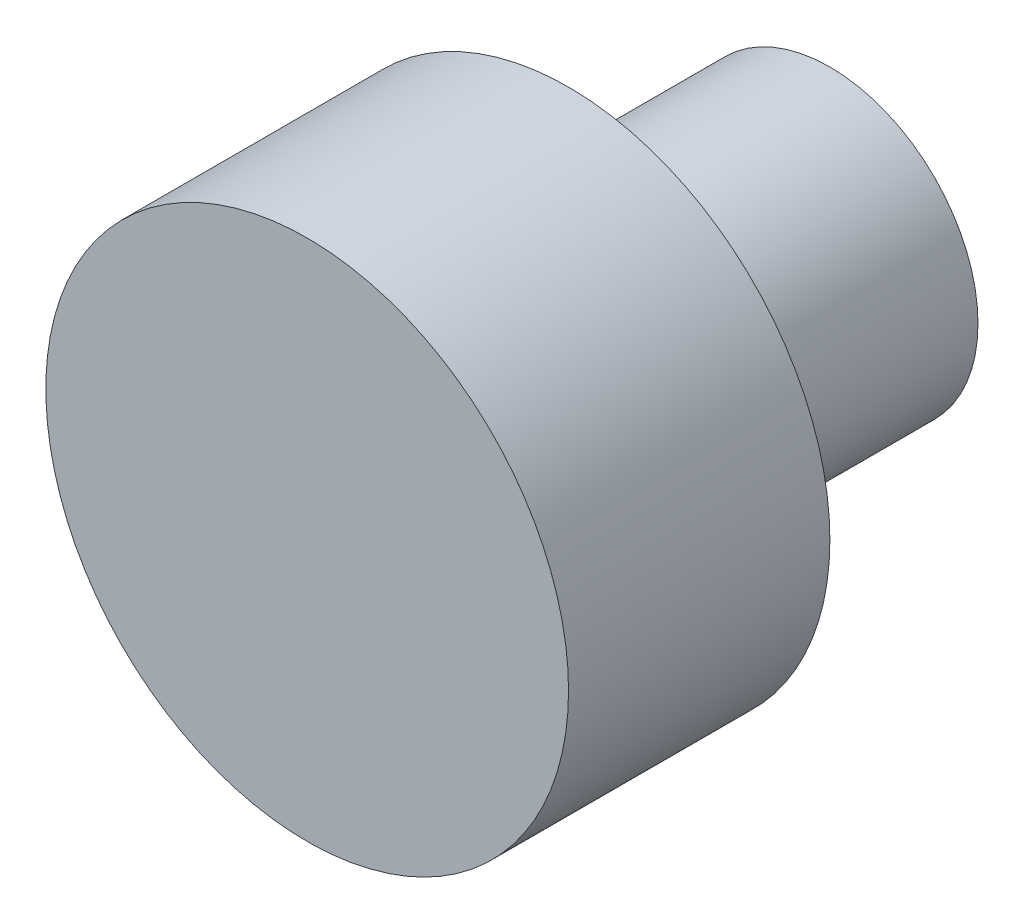
SolidWorks part; units mm, degrees
ref_plane "Front Plane" through (0, 0, 0) normal (0, 0, 1) x (1, 0, 0)
ref_plane "Top Plane" through (0, 0, 0) normal (0, 1, 0) x (1, 0, 0)
ref_plane "Right Plane" through (0, 0, 0) normal (1, 0, 0) x (0, 0, -1)
sketch "Sketch1" plane through (0, 0, 0) normal (0, 0, 1) x (1, 0, 0)
  circle A0 centre (0, 0) radius 6
  circle A1 centre (0, 0) radius 3.4
  dimension "D1" = 6.8
  dimension "D2" = 12
extrude "Boss-Extrude1" add sketch "Sketch1" along normal blind 6 contours A1 | A0 A1 region at (-5.8303, 0, 0) region at (0, 0, 0)
extrude "Boss-Extrude2" add sketch "Sketch1<3>" against normal blind 6 contours A1 region at (0, 0, 0)
sketch "Sketch1<3>" plane through (0, 0, 0) normal (0, 0, 1) x (1, 0, 0) same geometry as "Sketch1"
